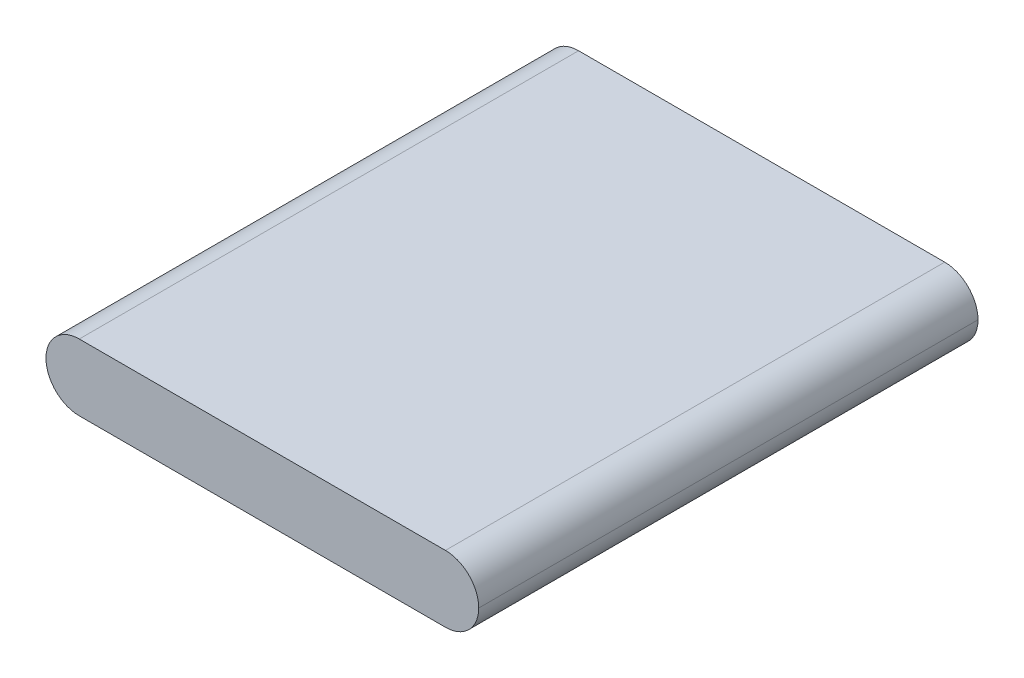
SolidWorks part; units mm, degrees
ref_plane "Front Plane" through (0, 0, 0) normal (0, 0, 1) x (1, 0, 0)
ref_plane "Top Plane" through (0, 0, 0) normal (0, 1, 0) x (1, 0, 0)
ref_plane "Right Plane" through (0, 0, 0) normal (1, 0, 0) x (0, 0, -1)
sketch "Sketch1" plane through (0, 0, 0) normal (0, 1, 0) x (1, 0, 0)
  line L1 (-16.51, -19.05) -> (16.51, -19.05)
  line L2 (-16.51, -19.05) -> (-16.51, 19.05)
  line L3 (-16.51, 19.05) -> (16.51, 19.05)
  line L4 (16.51, -19.05) -> (16.51, 19.05)
  line L5 (-16.51, -19.05) -> (16.51, 19.05) construction
  line L6 (-16.51, 19.05) -> (16.51, -19.05) construction
  point P0 (0, 0)
  dimension "D1" = 33.02
  dimension "D2" = 38.1
extrude "Boss-Extrude1" add sketch "Sketch1" along normal blind 5.08
fillet "Fillet1" radius 2.54 4 edges at (16.51, 0, 0) (16.51, 5.08, 0) (-16.51, 0, 0) (-16.51, 5.08, 0)
